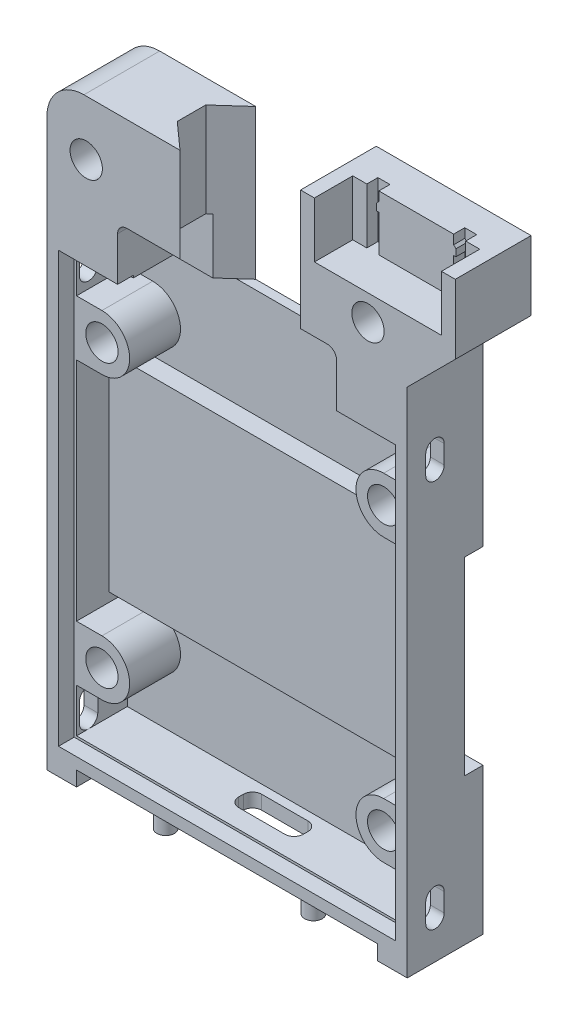
SolidWorks part; units mm, degrees
ref_plane "Front Plane" through (0, 0, 0) normal (0, 0, 1) x (1, 0, 0)
ref_plane "Top Plane" through (0, 0, 0) normal (0, 1, 0) x (1, 0, 0)
ref_plane "Right Plane" through (0, 0, 0) normal (1, 0, 0) x (0, 0, -1)
sketch "Sketch1" plane through (0, 0, 0) normal (0, 0, 1) x (1, 0, 0)
  line L0 (15.25, -20.35) -> (18, -20.35)
  line L1 (-19.5, -32.6) -> (19.5, -32.6)
  line L2 (-19.5, -32.6) -> (-19.5, 31.1)
  line L3 (-19.5, 31.1) -> (19.5, 31.1)
  line L4 (19.5, -32.6) -> (19.5, 31.1)
  line L5 (-15.25, -20.35) -> (-18, -20.35)
  line L6 (15.25, -26.35) -> (18, -26.35)
  line L7 (6.95, 31.1) -> (-15.5, 31.1) construction
  line L8 (-18, -31.1) -> (-18, 29.6)
  line L9 (-18, 29.6) -> (18, 29.6)
  line L10 (18, -31.1) -> (18, 29.6)
  line L11 (-18, -31.1) -> (18, -31.1)
  line L12 (-18, 14.9) -> (18, 14.9)
  line L13 (7.85, 14.9) -> (-4.95, 14.9) construction
  line L14 (-15.25, 4.15) -> (-18, 4.15)
  line L15 (-15.25, 10.15) -> (-18, 10.15)
  line L16 (15.25, 10.15) -> (18, 10.15)
  line L17 (15.25, 4.15) -> (18, 4.15)
  line L18 (-15.25, -26.35) -> (-18, -26.35)
  line L19 (19.5, -34.2) -> (19.5, -18.35) construction
  line L20 (-19.5, -34.2) -> (-19.5, -18.35) construction
  line L21 (15.3, -32.6) -> (-15.3, -32.6) construction
  line L22 (0, 31.1) -> (0, -32.6) construction
  line L23 (9.45, 26.9) -> (24.7, 26.9)
  line L24 (9.45, 26.9) -> (9.45, 33.9)
  line L25 (9.45, 33.9) -> (24.7, 33.9)
  line L26 (24.7, 26.9) -> (24.7, 33.9)
  line L27 (18, 29.6) -> (19.5, 31.1) construction
  line L28 (18.75, 30.35) -> (0, 30.35) construction
  line L29 (9.45, 26.9) -> (7.95, 26.9) construction
  line L30 (-7.95, 31.1) -> (7.95, 31.1)
  line L31 (-7.95, 31.1) -> (-7.95, 29.6)
  line L32 (-7.95, 29.6) -> (7.95, 29.6)
  line L33 (7.95, 31.1) -> (7.95, 29.6)
  line L34 (-7.95, 31.1) -> (7.95, 29.6) construction
  line L35 (-7.95, 29.6) -> (7.95, 31.1) construction
  line L36 (7.95, 26.9) -> (7.95, 29.6) construction
  line L37 (18, 29.6) -> (19.5, 29.6) construction
  line L38 (24.7, 26.4) -> (19.5, 21.2)
  line L39 (9.45, 33.9) -> (7.95, 33.9)
  line L40 (23.2, 33.9) -> (23.2, 26.9)
  line L41 (7.95, 33.9) -> (7.95, 31.1)
  line L42 (24.7, 30.4) -> (23.2, 30.4) construction
  line L43 (24.7, 26.9) -> (19.5, 26.9)
  line L44 (24.7, 26.9) -> (24.7, 26.4)
  line L45 (24.7, 26.4) -> (19.5, 26.4)
  line L46 (19.5, 26.9) -> (19.5, 26.4)
  circle A0 centre (15.25, -23.35) radius 1.75
  arc A1 (-15.5, 31.1) -> (-19.5, 27.1) centre (-15.5, 27.1) ccw construction
  circle A2 centre (15.25, -23.35) radius 3
  arc A3 (-15.5, 31.1) -> (-19.5, 27.1) centre (-15.5, 27.1) ccw
  arc A4 (-15.5, 29.6) -> (-18, 27.1) centre (-15.5, 27.1) ccw
  circle A6 centre (-15.25, -23.35) radius 1.75
  circle A7 centre (-15.25, -23.35) radius 1.75
  circle A8 centre (-15.25, 7.15) radius 1.75
  circle A9 centre (15.25, 7.15) radius 1.75
  circle A10 centre (15.25, 25.15) radius 1.75
  circle A11 centre (-15.25, 25.15) radius 1.75
  circle A12 centre (-15.25, -23.35) radius 3
  circle A13 centre (-15.25, -23.35) radius 3
  circle A14 centre (15.25, 7.15) radius 3
  circle A15 centre (-15.25, 7.15) radius 3
  dimension "D2" = 1.5
  dimension "D4" = 6
  dimension "D3" = 3.5
  dimension "D5" = 13.75
  dimension "D6" = 15.9
  dimension "D7" = 7
  dimension "D8" = 45
  dimension "D9" = 0.5
  dimension "D1" = 1.5
extrude "Base shape" add sketch "Sketch1" along normal up to surface (8.2 mm away) contours A15 L8 L9 L31 L3 A3 L2 L1 L4 L23 L10 A14 A2 L11 A12 | A12 L8 L18 | A12 L8 A6 | L8 A12 | A12 L5 L8 | A15 L8 L14 | A15 L8 A8 | L8 A15 | A15 L15 L8 | L23 A10 L24 L9 A4 L8 L12 L10 A11 | A4 L9 L8 | L33 L3 L31 L9 | L3 L33 L9 L24 | L24 L9 L10 L23 L4 L3 | L24 L23 L10 L9 | A14 L10 L16 | L10 A14 A9 | A14 L17 L10 | L10 A14 | L10 A2 L6 | A2 L10 A0 | L0 A2 L10 | A2 L10 | L40 L25 L24 L3 L4 L23 | L25 L40 L23 L26 | L38 L45 L4 | L45 L44 L23 L4 | L39 L41 L3 L24 region at (16.8481, -20.9099, 0) region at (17.3601, -20.8437, 0) region at (18.7469, -8.1, 0) region at (17.3601, -25.8563, 0) region at (18.1004, -23.35, 0) region at (17.3601, 4.6437, 0) region at (16.8481, 4.7099, 0) region at (18.1004, 7.15, 0) region at (17.3601, 9.6563, 0) region at (-17.3601, -25.8563, 0) region at (-0.6044, 21.831, 0) region at (-18.1004, -23.35, 0) region at (-17.9169, -23.35, 0) region at (13.725, 28.25, 0) region at (15.3803, 29.9053, 0) region at (-17.3601, -20.8437, 0) region at (22.1, 26.65, 0) region at (17.77, 31.4935, 0) region at (-17.3601, 9.6563, 0) region at (-17.4416, 29.0416, 0) region at (8.7, 30.35, 0) region at (21.2333, 24.6667, 0) region at (23.95, 30.4, 0) region at (-16.8481, 9.5901, 0) region at (-18.1004, 7.15, 0) region at (-17.3601, 4.6437, 0) region at (0, 30.35, 0) region at (8.7, 32.5, 0)
sketch "Sketch3" plane through (19.5, 0, 0) normal (1, 0, 0) x (0, 0, -1)
  line L1 (0, -18.35) -> (-2, -18.35)
  line L2 (0, -18.35) -> (0, 2.15)
  line L3 (0, 2.15) -> (-2, 2.15)
  line L4 (-2, -18.35) -> (-2, 2.15)
  line L5 (0, -18.35) -> (1.75, -18.35) construction
  line L6 (0, 2.15) -> (1.75, 2.15) construction
  line L7 (0, -32.6) -> (0, 21.2) construction
  dimension "D1" = 2
extrude "Strap cut" cut sketch "Sketch3" against normal through all
sketch "Sketch4" plane through (0, 31.1, 0) normal (0, 1, 0) x (1, 0, 0)
  line L2 (7.95, 0) -> (-5.0998, 0)
  line L4 (-15.5, 0) -> (7.95, 0) construction
  line L5 (-15.5, -8.2) -> (7.95, -8.2) construction
  line L6 (7.95, -8.2) -> (-5.0998, -8.2)
  line L12 (7.95, -8.3) -> (7.95, 0.1)
  line L13 (7.95, 0.1) -> (-4.9883, 0.1)
  line L14 (-4.9883, 0.1) -> (-7.95, -2.5553)
  line L15 (-7.95, -2.5553) -> (-7.95, -5.6447)
  line L16 (-7.95, -5.6447) -> (-4.9883, -8.3)
  line L17 (-4.9883, -8.3) -> (7.95, -8.3)
  line L18 (7.95, -8.3) -> (7.95, 0.1)
  line L19 (7.95, 0.1) -> (-4.9883, 0.1)
  line L20 (-4.9883, 0.1) -> (-7.95, -2.5553)
  line L21 (-7.95, -2.5553) -> (-7.95, -5.6447)
  line L22 (-7.95, -5.6447) -> (-4.9883, -8.3)
  line L23 (-4.9883, -8.3) -> (7.95, -8.3)
  dimension "D1" = 0.1
extrude "XT60 cut" cut sketch "Sketch4" against normal up to next contours L21 L22 L18 L20 region at (0.4142, 31.1, 4.1)
sketch "Sketch5" plane through (19.5, 0, 0) normal (1, 0, 0) x (0, 0, -1)
  line L1 (-8.2, -32.6) -> (-8.2, 21.2) construction
  line L2 (-6.2, -31.1) -> (-4.2, -31.1)
  line L3 (-6.2, -31.1) -> (-6.2, -27.1)
  line L4 (-6.2, -27.1) -> (-4.2, -27.1)
  line L5 (-4.2, -31.1) -> (-4.2, -27.1)
  line L6 (-8.2, -31.1) -> (0, -31.1) construction
  line L7 (-8.2, 14.9) -> (0, 14.9) construction
  line L8 (-6.2, 14.9) -> (-4.2, 14.9)
  line L9 (-6.2, 14.9) -> (-6.2, 10.9)
  line L10 (-6.2, 10.9) -> (-4.2, 10.9)
  line L11 (-4.2, 14.9) -> (-4.2, 10.9)
  line L14 (-5.2, -27.1) -> (-5.2, -31.1) construction
  line L15 (-5.2, 14.9) -> (-5.2, 10.9) construction
  circle A0 centre (-5.2, -28.1) radius 1
  circle A1 centre (-5.2, -30.1) radius 1
  circle A2 centre (-5.2, 13.9) radius 1
  circle A3 centre (-5.2, 11.9) radius 1
  point P20 (-5.2, -29.1)
  point P31 (-5.2, 12.9)
  dimension "D3" = 4
  dimension "D1" = 2
  dimension "D2" = 2
extrude "Power wires cut" cut sketch "Sketch5" against normal through all contours A2 | A3 | A3 A2 L9 | A3 L11 A2 | A1 | A0 | A1 L5 A0 | A1 A0 L3 region at (19.5, -30.1, 5.2) region at (19.5, -29.1, 5.9766) region at (19.5, -29.1, 4.4234) region at (19.5, -28.1, 5.2) region at (19.5, 13.9, 5.2) region at (19.5, 12.9, 5.9766) region at (19.5, 12.9, 4.4234) region at (19.5, 11.9, 5.2)
sketch "Sketch6" plane through (0, 0, 8.2) normal (0, 0, 1) x (1, 0, 0)
  line L0 (9.15, 14.9) -> (10.85, 14.9) construction
  line L1 (-11.85, 19.9) -> (11.85, 19.9)
  line L2 (-11.85, 19.9) -> (-11.85, 14.9)
  line L3 (-11.85, 14.9) -> (11.85, 14.9)
  line L4 (11.85, 19.9) -> (11.85, 14.9)
  line L5 (-10.85, 20.9) -> (10.85, 20.9)
  arc A0 (11.85, 19.9) -> (10.85, 20.9) centre (10.85, 19.9) ccw construction
  arc A1 (-10.85, 20.9) -> (-11.85, 19.9) centre (-10.85, 19.9) ccw construction
  arc A2 (11.85, 19.9) -> (10.85, 20.9) centre (10.85, 19.9) ccw
  arc A3 (-10.85, 20.9) -> (-11.85, 19.9) centre (-10.85, 19.9) ccw
  line M1 (7.95, 33.9) -> (7.95, 14.9)
  line M15 (-5.0998, 14.9) -> (-5.0998, 31.1)
  line M118 (7.95, 14.9) -> (18, 14.9)
  line M134 (-18, 14.9) -> (-5.0998, 14.9)
extrude "IO wires cut" cut sketch "Sketch6" against normal blind 6 contours L5 A3 L1 M15 | L1 L2 M134 M15 | L5 L1 M15 M1 | L3 L1 M15 M1 | L1 A2 L5 M1 | L4 L1 M1 M118 region at (-8.3714, 20.3909, 8.2) region at (-8.4749, 17.4, 8.2) region at (1.4251, 20.4, 8.2) region at (1.4251, 17.4, 8.2) region at (9.7995, 20.3839, 8.2) region at (9.9, 17.4, 8.2)
sketch "Sketch7" plane through (-18, 0, 0) normal (1, 0, 0) x (0, 0, -1)
  line L6 (0, -18.35) -> (0, -20.35)
  line L7 (-2, -18.35) -> (0, -18.35)
  line L8 (-2, 2.15) -> (-2, -18.35)
  line L9 (0, 2.15) -> (-2, 2.15)
  line L12 (0, 3.15) -> (-3, 3.15)
  line L13 (-3, 3.15) -> (-3, -19.35)
  line L14 (-3, -19.35) -> (-1, -19.35)
  line L15 (-1, -19.35) -> (-1, -20.35)
  line L16 (-1, -20.35) -> (0, -20.35)
  line L17 (0, 3.15) -> (-1, 3.15)
  line L19 (0, -31.1) -> (-1, -31.1)
  line L22 (0, -31.1) -> (0, -20.35)
  line L23 (0, -20.35) -> (-1, -20.35)
  line L24 (-1, -31.1) -> (-1, -20.35)
  line L25 (0, 3.15) -> (0, 14.9)
  line L26 (0, 14.9) -> (-1, 14.9)
  line L27 (-1, 3.15) -> (-1, 14.9)
  line L28 (-5.2, 14.9) -> (0, 14.9) construction
  line L31 (0, -20.35) -> (0, -18.35) construction
  line L32 (0, 2.15) -> (-2, 2.15) construction
  line M48 (0, -20.35) -> (0, -18.35)
  line M49 (0, -18.35) -> (-2, -18.35)
  line M50 (-2, -18.35) -> (-2, 2.15)
  line M51 (-2, 2.15) -> (0, 2.15)
  line M52 (0, 2.15) -> (0, 4.15)
  line M53 (0, 4.15) -> (-8.2, 4.15)
  line M55 (-8.2, -20.35) -> (0, -20.35)
  dimension "D1" = 1
extrude "Bottom" add sketch "Sketch7" along normal up to surface (36 mm away) contours L27 L25 L26 M53 | L27 L12 M52 M53 | L14 L15 L12 L13 M55 M48 M49 M50 M51 M52 | L24 L19 L22 M55 region at (-18, -8.5273, 2.2091) region at (-18, -25.725, 0.5) region at (-18, 3.65, 0.5) region at (-18, 9.525, 0.5) up to face at (18, -8.1, 2.55)
sketch "Sketch9" plane through (0, 0, 0) normal (0, 0, -1) x (-1, 0, 0)
  circle A0 centre (15.25, -23.35) radius 1.75 construction
  circle A1 centre (-15.25, 7.15) radius 1.75 construction
  circle A2 centre (15.25, 7.15) radius 1.75 construction
  circle A3 centre (15.25, -23.35) radius 1.75 construction
  circle A4 centre (15.25, -23.35) radius 1.75
  circle A5 centre (-15.25, 7.15) radius 1.75
  circle A6 centre (15.25, 7.15) radius 1.75
  circle A7 centre (15.25, -23.35) radius 1.75
  circle A8 centre (-15.25, -23.35) radius 1.75 construction
  circle A9 centre (-15.25, -23.35) radius 1.75
extrude "Bottom holes" cut sketch "Sketch9" against normal up to next contours A5 | A6 | A4 | A9 region at (-15.25, -23.35, 0) region at (15.25, 7.15, 0) region at (-15.25, 7.15, 0) region at (15.25, -23.35, 0)
sketch "Sketch8" plane through (0, 0, 8.2) normal (0, 0, 1) x (1, 0, 0)
  line L0 (-6.2152, 14.9) -> (-18, 14.9) construction
  line L1 (-18.25, 15.15) -> (18.25, 15.15)
  line L2 (-18.25, 15.15) -> (-18.25, -31.35)
  line L3 (-18.25, -31.35) -> (18.25, -31.35)
  line L4 (18.25, 15.15) -> (18.25, -31.35)
  line L5 (-18, 14.9) -> (-18.25, 14.9) construction
  line L6 (-18, 14.9) -> (-18, 15.15) construction
  line L7 (18, 14.9) -> (18.25, 14.9) construction
  line L8 (-18, -31.1) -> (-18, -31.35) construction
  dimension "D1" = 0.25
extrude "PCB cut" cut sketch "Sketch8" against normal blind 1.7
sketch "Sketch11" plane through (0, -32.6, 0) normal (0, -1, 0) x (1, 0, 0)
  line L0 (19.5, 8.2) -> (19.5, 0) construction
  line L1 (-19.5, 8.2) -> (19.5, 8.2)
  line L2 (-19.5, 8.2) -> (-19.5, -1.8)
  line L3 (-19.5, -1.8) -> (19.5, -1.8)
  line L4 (19.5, 8.2) -> (19.5, -1.8)
  line L5 (-19.5, 3.2) -> (19.5, 3.2) construction
  line L6 (0, -1.8) -> (0, 8.2) construction
  line L8 (-2.5, 4.45) -> (2.5, 4.45)
  line L9 (-3.5, 3.45) -> (-3.5, 2.95)
  line L10 (-2.5, 1.95) -> (2.5, 1.95)
  line L11 (3.5, 3.45) -> (3.5, 2.95)
  line L12 (-3.5, 4.45) -> (3.5, 1.95) construction
  line L13 (-3.5, 1.95) -> (3.5, 4.45) construction
  arc A0 (2.5, 4.45) -> (3.5, 3.45) centre (2.5, 3.45) cw
  arc A1 (2.5, 1.95) -> (3.5, 2.95) centre (2.5, 2.95) ccw
  arc A2 (-3.5, 2.95) -> (-2.5, 1.95) centre (-2.5, 2.95) ccw
  arc A3 (-2.5, 4.45) -> (-3.5, 3.45) centre (-2.5, 3.45) ccw
  point P11 (0, 3.2)
  dimension "D4" = 1
  dimension "D1" = 10
  dimension "D2" = 7
  dimension "D3" = 2.5
extrude "Ledbar wires cut" cut sketch "Sketch11" against normal up to next contours L8 A3 L9 A2 L10 A1 L11 A0 region at (0, -32.6, 3.2)
sketch "Sketch13" plane through (0, -32.6, 0) normal (0, -1, 0) x (1, 0, 0)
  line L0 (-19.5, 8.2) -> (19.5, 8.2) construction
  line L1 (19.5, 0) -> (16.3, 0)
  line L2 (19.5, 0) -> (19.5, 8.2)
  line L3 (19.5, 8.2) -> (16.3, 8.2)
  line L4 (16.3, 0) -> (16.3, 8.2)
  line L5 (16.1, -1.8) -> (16.1, 8.2) construction
  line L6 (0, 8.2) -> (0, 0) construction
  line L7 (-19.5, 0) -> (-16.3, 0)
  line L8 (-19.5, 0) -> (-19.5, 8.2)
  line L9 (-19.5, 8.2) -> (-16.3, 8.2)
  line L10 (-16.3, 0) -> (-16.3, 8.2)
  dimension "D1" = 0.2
extrude "Ledbar sides" add sketch "Sketch13" along normal blind 1.6
sketch "Sketch14" plane through (0, -32.6, 0) normal (0, -1, 0) x (1, 0, 0)
  circle A0 centre (8, 6.85) radius 0.95
  circle A1 centre (-8, 6.85) radius 0.95
  dimension "D1" = 1.9
extrude "Ledbar mounts" add sketch "Sketch14" along normal blind 2
sketch "Sketch16" plane through (0, 33.9, 0) normal (0, 1, 0) x (1, 0, 0)
  line L0 (7.95, -6.125) -> (24.7, -6.125) construction
  line L1 (7.95, -8.2) -> (24.7, -8.2) construction
  line L2 (21.675, -2.85) -> (20.375, -2.85)
  line L3 (20.375, -4.05) -> (20.375, -2.85)
  line L4 (9.45, -4.05) -> (23.2, -4.05)
  line L5 (9.45, -4.05) -> (9.45, -8.2)
  line L6 (9.45, -8.2) -> (23.2, -8.2)
  line L7 (23.2, -4.05) -> (23.2, -8.2)
  line L8 (9.45, -4.05) -> (23.2, -8.2) construction
  line L9 (9.45, -8.2) -> (23.2, -4.05) construction
  line L10 (24.7, -8.2) -> (24.7, 0) construction
  line L11 (7.95, -8.2) -> (7.95, 0) construction
  line L12 (16.325, -8.2) -> (16.325, -4.05) construction
  line L13 (11.625, -2.85) -> (11.625, -4.05) construction
  line L14 (10.975, -4.05) -> (12.275, -4.05)
  line L15 (10.975, -4.05) -> (10.975, -2.85)
  line L16 (10.975, -2.85) -> (12.275, -2.85)
  line L17 (12.275, -4.05) -> (12.275, -2.85)
  line L18 (10.975, -2.85) -> (10.975, -8.2) construction
  line L19 (21.675, -4.05) -> (21.675, -2.85)
  point P6 (16.325, -6.125)
  dimension "D1" = 13.75
  dimension "D2" = 4.15
  dimension "D3" = 1.3
  dimension "D4" = 1.2
  dimension "D5" = 4.7
extrude "Balance plug cut" cut sketch "Sketch16" against normal blind 6 contours L7 L4 L5 L6 | L4 L17 L16 L15 | L4 L19 L2 L3 region at (21.025, 33.9, 3.45) region at (16.325, 33.9, 6.125) region at (11.625, 33.9, 3.45)
sketch "Sketch17" plane through (0, 0, 2.85) normal (0, 0, 1) x (1, 0, 0)
  line L0 (16.325, 33.9) -> (16.325, 27.9) construction
  line L1 (12.275, 33.9) -> (20.375, 33.9) construction
  line L2 (12.275, 27.9) -> (20.375, 27.9) construction
  line L3 (12.275, 27.9) -> (12.275, 33.9) construction
  line L4 (12.025, 32.9) -> (20.625, 32.9)
  line L5 (12.025, 32.9) -> (12.025, 31.9)
  line L6 (12.025, 31.9) -> (20.625, 31.9)
  line L7 (20.625, 32.9) -> (20.625, 31.9)
  line L8 (12.025, 32.9) -> (20.625, 31.9) construction
  line L9 (12.025, 31.9) -> (20.625, 32.9) construction
  line L10 (12.025, 32.65) -> (12.275, 32.9)
  line L11 (20.625, 32.65) -> (20.375, 32.9)
  point P6 (16.325, 32.4)
  line M7 (20.375, 33.9) -> (20.375, 27.9)
  dimension "D1" = 0.25
  dimension "D2" = 1
  dimension "D3" = 1
  dimension "D4" = 45
extrude "Balance plug locks" add sketch "Sketch17" along normal up to surface (1.2 mm away) contours L10 L5 L6 L4 M7 | L7 L11 L6 M7 region at (16.2154, 32.3984, 2.85) region at (20.494, 32.3405, 2.85) up to face at (16.325, 30.9, 4.05)
sketch "Sketch10" [suppressed] plane through (0, 0, 2) normal (0, 0, -1) x (-1, 0, 0)
  line L0 (0, 2.15) -> (0, -18.35) construction
  line L1 (19.5, 2.15) -> (-19.5, 2.15) construction
  line L2 (19.5, -18.35) -> (-19.5, -18.35) construction
  line L3 (19.5, 2.15) -> (19.5, -18.35) construction
  line L4 (-19.5, 1.15) -> (19.5, 1.15)
  line L5 (-19.5, 1.15) -> (-19.5, 0.65)
  line L6 (-19.5, 0.65) -> (19.5, 0.65)
  line L7 (19.5, 1.15) -> (19.5, 0.65)
  line L8 (-19.5, 1.15) -> (19.5, 0.65) construction
  line L9 (-19.5, 0.65) -> (19.5, 1.15) construction
  line L10 (-19.5, 2.15) -> (19.5, 2.15) construction
  line L11 (-19.5, -1.35) -> (19.5, -1.35)
  line L12 (19.5, -0.85) -> (19.5, -1.35)
  line L13 (-19.5, -0.85) -> (19.5, -0.85)
  line L14 (-19.5, -0.85) -> (-19.5, -1.35)
  line L15 (-19.5, -3.35) -> (19.5, -3.35)
  line L16 (19.5, -2.85) -> (19.5, -3.35)
  line L17 (-19.5, -2.85) -> (19.5, -2.85)
  line L18 (-19.5, -2.85) -> (-19.5, -3.35)
  line L19 (-19.5, -5.35) -> (19.5, -5.35)
  line L20 (19.5, -4.85) -> (19.5, -5.35)
  line L21 (-19.5, -4.85) -> (19.5, -4.85)
  line L22 (-19.5, -4.85) -> (-19.5, -5.35)
  line L23 (-19.5, -7.35) -> (19.5, -7.35)
  line L24 (19.5, -6.85) -> (19.5, -7.35)
  line L25 (-19.5, -6.85) -> (19.5, -6.85)
  line L26 (-19.5, -6.85) -> (-19.5, -7.35)
  line L27 (-19.5, -9.35) -> (19.5, -9.35)
  line L28 (19.5, -8.85) -> (19.5, -9.35)
  line L29 (-19.5, -8.85) -> (19.5, -8.85)
  line L30 (-19.5, -8.85) -> (-19.5, -9.35)
  line L31 (-19.5, -11.35) -> (19.5, -11.35)
  line L32 (19.5, -10.85) -> (19.5, -11.35)
  line L33 (-19.5, -10.85) -> (19.5, -10.85)
  line L34 (-19.5, -10.85) -> (-19.5, -11.35)
  line L35 (-19.5, -13.35) -> (19.5, -13.35)
  line L36 (19.5, -12.85) -> (19.5, -13.35)
  line L37 (-19.5, -12.85) -> (19.5, -12.85)
  line L38 (-19.5, -12.85) -> (-19.5, -13.35)
  line L39 (-19.5, -15.35) -> (19.5, -15.35)
  line L40 (19.5, -14.85) -> (19.5, -15.35)
  line L41 (-19.5, -14.85) -> (19.5, -14.85)
  line L42 (-19.5, -14.85) -> (-19.5, -15.35)
  line L43 (-19.5, -17.35) -> (19.5, -17.35)
  line L44 (19.5, -16.85) -> (19.5, -17.35)
  line L45 (-19.5, -16.85) -> (19.5, -16.85)
  line L46 (-19.5, -16.85) -> (-19.5, -17.35)
  point P6 (0, 0.9)
  dimension "D1" = 1
  dimension "D2" = 0.5
  dimension "D4" = 2
  dimension "D3" = 10
extrude "3D print ribs" [suppressed] add sketch "Sketch10" along normal up to surface (2 mm away) up to face at (-17, 7.15, 0)
sketch "Sketch15" [suppressed] plane through (0, 0, 0) normal (0, 0, -1) x (-1, 0, 0)
  line L0 (-8, -34.6) -> (-8, -32.6) construction
  line L1 (-8.95, -34.6) -> (-7.05, -34.6) construction
  line L2 (-8.95, -32.6) -> (-7.05, -32.6) construction
  line L3 (0, -32.6) -> (0, 14.9) construction
  line L4 (-8.25, -34.6) -> (-7.75, -34.6)
  line L5 (-8.25, -34.6) -> (-8.25, -32.6)
  line L6 (-8.25, -32.6) -> (-7.75, -32.6)
  line L7 (-7.75, -34.6) -> (-7.75, -32.6)
  line L8 (-8.25, -34.6) -> (-7.75, -32.6) construction
  line L9 (-8.25, -32.6) -> (-7.75, -34.6) construction
  line L10 (16.3, -32.6) -> (-16.3, -32.6) construction
  line L11 (-7.95, 14.9) -> (5.0998, 14.9) construction
  line L12 (8.25, -32.6) -> (7.75, -32.6)
  line L13 (7.75, -34.6) -> (7.75, -32.6)
  line L14 (8.25, -34.6) -> (7.75, -34.6)
  line L15 (8.25, -34.6) -> (8.25, -32.6)
  point P6 (-8, -33.6)
  dimension "D1" = 0.5
extrude "3D print led supports" [suppressed] add sketch "Sketch15" against normal up to next
